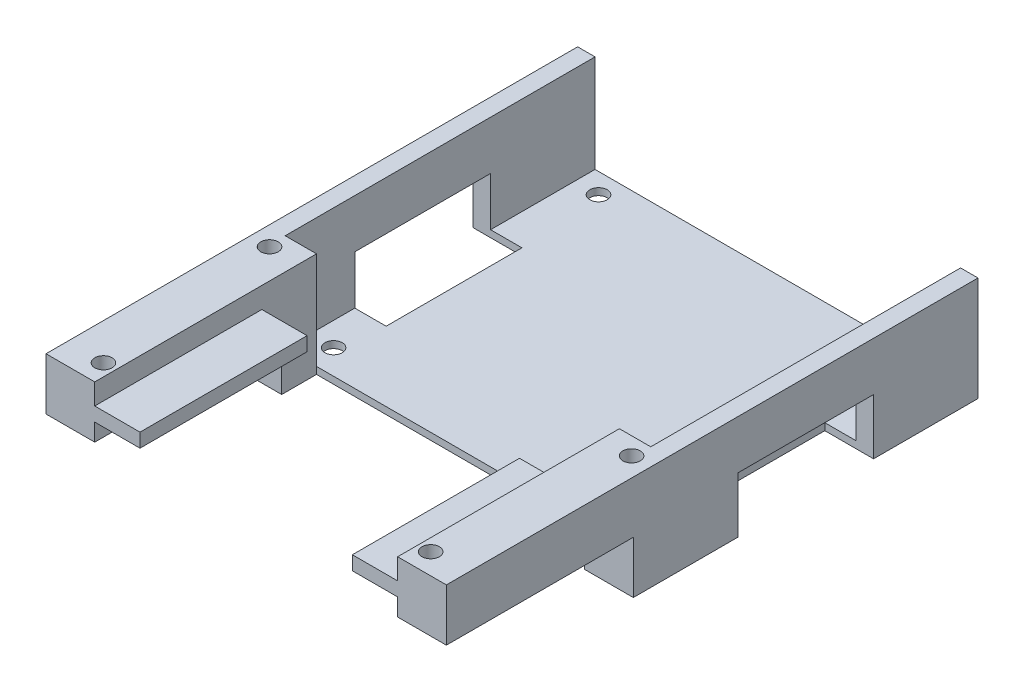
SolidWorks part; units mm, degrees
ref_plane "Front Plane" through (0, 0, 0) normal (0, 0, 1) x (1, 0, 0)
ref_plane "Top Plane" through (0, 0, 0) normal (0, 1, 0) x (1, 0, 0)
ref_plane "Right Plane" through (0, 0, 0) normal (1, 0, 0) x (0, 0, -1)
sketch "Sketch1" plane through (0, 0, 0) normal (0, 1, 0) x (1, 0, 0)
  line L0 (0, 0) -> (0, 76.35) construction
  line L1 (-28.75, 76.35) -> (28.75, 76.35)
  line L2 (28.75, 76.35) -> (28.75, 0)
  line L3 (28.75, 0) -> (21.75, 0)
  line L4 (21.75, 0) -> (21.75, 31.85)
  line L5 (21.75, 31.85) -> (-21.75, 31.85)
  line L6 (-21.75, 31.85) -> (-21.75, 0)
  line L7 (-21.75, 0) -> (-28.75, 0)
  line L8 (-28.75, 0) -> (-28.75, 76.35)
  line L9 (-26.25, 76.35) -> (-26.25, 31.85)
  line L14 (-26.25, 31.85) -> (-21.75, 31.85)
  line L15 (26.25, 76.35) -> (26.25, 31.85)
  line L16 (26.25, 31.85) -> (21.75, 31.85)
  line L17 (28.75, 74.35) -> (30.25, 74.35)
  line L18 (-28.75, 41.35) -> (-26.25, 41.35)
  line L19 (-28.75, 41.35) -> (-28.75, 53.35)
  line L20 (-28.75, 53.35) -> (-26.25, 53.35)
  line L21 (-26.25, 41.35) -> (-26.25, 53.35)
  line L22 (30.25, 68.35) -> (28.75, 68.35)
  line L23 (-30.25, 68.35) -> (-28.75, 68.35)
  line L24 (-28.75, 74.35) -> (-30.25, 74.35)
  arc A0 (30.25, 68.35) -> (30.25, 74.35) centre (30.25, 71.35) ccw
  arc A1 (-30.25, 68.35) -> (-30.25, 74.35) centre (-30.25, 71.35) cw
  point P10 (0, 76.35)
  point P16 (-27.5, 41.35)
  point P17 (-22.85, 73.45)
  point P18 (22.85, 73.45)
  point P23 (22.85, 35.4)
  point P24 (-22.85, 35.4)
  point P25 (23.5, 3)
  point P26 (26, 29.35)
  point P27 (-26, 29.35)
  point P28 (-23.5, 3)
  point P40 (30.25, 71.35)
  point P41 (-30.25, 71.35)
  dimension "D16" = 3
  dimension "D1" = 2.5
  dimension "D2" = 7
  dimension "D3" = 43.5
  dimension "D4" = 31.85
  dimension "D5" = 44.5
  dimension "D6" = 23
  dimension "D7" = 12
  dimension "D8" = 22.85
  dimension "D9" = 38.05
  dimension "D10" = 2.9
  dimension "D11" = 47
  dimension "D12" = 52
  dimension "D13" = 47
  dimension "D14" = 3
  dimension "D15" = 1.5
  dimension "D17" = 2
extrude "Boss-Extrude1" add sketch "Sketch1" along normal blind 1 contours L5 L0 L1 L9 L14 | L0 L5 L16 L15 L1 region at (-13.125, 0, -54.1) region at (13.125, 0, -54.1)
extrude "Boss-Extrude2" add sketch "Sketch1<3>" along normal blind 15 contours L18 L8 L7 L6 L14 L9 | L8 L20 L9 L1 | L15 L16 L4 L3 L2 L1 | L20 L8 L18 L9 region at (-27.5, 0, -64.85) region at (25.999, 0, -28.6329) region at (-27.5, 0, -47.35) region at (-25.4666, 0, -17.9154)
sketch "Sketch1<3>" plane through (0, 0, 0) normal (0, 1, 0) x (1, 0, 0) same geometry as "Sketch1"
hole_wizard "Ø2.5 (2.5) Diameter Hole1" positions "Sketch4" profile "Sketch5" hole size "Ø2.5" standard "ANSI Metric" end condition through all
sketch "Sketch4" plane through (0, 0, 0) normal (0, -1, 0) x (-1, 0, 0)
  point P0 (-22.85, 73.45)
  point P3 (22.85, 73.45)
  point P6 (26, 29.35)
  point P9 (22.85, 35.4)
  point P12 (-22.85, 35.4)
  point P15 (-26, 29.35)
  point P18 (-23.5, 3)
  point P21 (23.5, 3)
  point P24 (-30.25, 71.35)
  point P27 (30.25, 71.35)
sketch "Sketch5" plane through (22.85, 0, -73.45) normal (1, 0, 0) x (0, 0, -1)
  line L0 (0, 0) -> (0, 15)
  line L1 (0, 15) -> (1.25, 15)
  line L2 (1.25, 15) -> (1.25, 0)
  line L5 (1.25, 0) -> (0, 0)
  line L11 (0, -6.35) -> (0, 107.95) construction
  dimension "Thru Hole Dia." = 2.5
  dimension "Thru Hole Depth" = 15
sketch "Sketch6" plane through (0, 0, 0) normal (0, 0, 1) x (1, 0, 0)
  line L0 (-21.75, 15) -> (-21.75, 0) construction
  line L5 (0, -1.6497) -> (0, 21.9352) construction
  line L6 (-21.75, 10) -> (-15.25, 10)
  line L7 (-21.75, 10) -> (-21.75, 12)
  line L8 (-21.75, 12) -> (-15.25, 12)
  line L9 (-15.25, 10) -> (-15.25, 12)
  line L10 (-28.75, 15) -> (-28.75, 0) construction
  line L11 (-20.25, 10) -> (-21.75, 10)
  line L12 (-20.25, 10) -> (-20.25, 7.5)
  line L13 (-20.25, 7.5) -> (-21.75, 7.5)
  line L14 (-21.75, 10) -> (-21.75, 7.5)
  line L15 (-21.75, 0) -> (-28.75, 0)
  line L16 (-21.75, 0) -> (-21.75, 7.5)
  line L17 (-21.75, 7.5) -> (-28.75, 7.5)
  line L18 (-28.75, 0) -> (-28.75, 7.5)
  line L19 (28.75, 0) -> (28.75, 7.5)
  line L20 (21.75, 7.5) -> (28.75, 7.5)
  line L21 (21.75, 0) -> (21.75, 7.5)
  line L22 (21.75, 0) -> (28.75, 0)
  line L23 (21.75, 10) -> (21.75, 7.5)
  line L24 (20.25, 7.5) -> (21.75, 7.5)
  line L25 (20.25, 10) -> (20.25, 7.5)
  line L26 (20.25, 10) -> (21.75, 10)
  line L27 (15.25, 10) -> (15.25, 12)
  line L28 (21.75, 12) -> (15.25, 12)
  line L29 (21.75, 10) -> (21.75, 12)
  line L30 (21.75, 10) -> (15.25, 10)
  line L31 (-21.75, 15) -> (-28.75, 15) construction
  line M21 (21.75, 0) -> (28.75, 0)
  line M22 (28.75, 0) -> (28.75, 15)
  line M24 (21.75, 15) -> (21.75, 0)
  dimension "D1" = 6.5
  dimension "D2" = 3
  dimension "D3" = 2
  dimension "D4" = 2.5
  dimension "D5" = 1.5
extrude "Boss-Extrude3" add sketch "Sketch6" against normal blind 24 contours L30 L26 L28 L27 M24 | L6 L9 L8 L7 region at (-18.5, 11, 0) region at (18.5, 11, 0)
extrude "Cut-Extrude1" cut sketch "Sketch6<4>" against normal blind 26.85 contours L18 L15 L16 L17 | L20 M24 M21 M22 region at (-25.25, 3.75, 0) region at (25.25, 3.75, 0)
sketch "Sketch6<4>" plane through (0, 0, 0) normal (0, 0, 1) x (1, 0, 0) same geometry as "Sketch6"
sketch "Sketch8" plane through (0, 0, 0) normal (0, -1, 0) x (1, 0, 0)
  line L0 (0, 17.5937) -> (0, -89.2896) construction
  line L1 (-28.75, -61.35) -> (-21.75, -61.35)
  line L2 (-28.75, -61.35) -> (-28.75, -41.85)
  line L3 (-28.75, -41.85) -> (-21.75, -41.85)
  line L4 (-21.75, -61.35) -> (-21.75, -41.85)
  line L6 (-28.75, -76.35) -> (28.75, -76.35) construction
  line L8 (21.75, -61.35) -> (21.75, -41.85)
  line L9 (28.75, -41.85) -> (21.75, -41.85)
  line L10 (28.75, -61.35) -> (28.75, -41.85)
  line L11 (28.75, -61.35) -> (21.75, -61.35)
  line L12 (-28.75, -26.85) -> (-28.75, -76.35) construction
  dimension "D1" = 15
  dimension "D2" = 7
  dimension "D3" = 19.5
extrude "Cut-Extrude2" cut sketch "Sketch8" against normal blind 8
sketch "Sketch9" plane through (0, 0, 0) normal (0, -1, 0) x (1, 0, 0)
  line L0 (-3.6898, -66.9636) -> (-0.7669, -56.1918)
  line L1 (-0.7669, -56.1918) -> (-9.5993, -56.1918)
  line L2 (-9.5993, -56.1918) -> (4.2079, -40.0618)
  line L3 (4.2079, -40.0618) -> (3.001, -51.0446)
  line L4 (3.001, -51.0446) -> (10.9951, -51.0446)
  line L5 (10.9951, -51.0446) -> (-3.6898, -66.9636)
extrude "Cut-Extrude3" cut sketch "Sketch9" against normal blind 0.3
equation "\"D1@Boss-Extrude2\"=16.000000mm-1"
